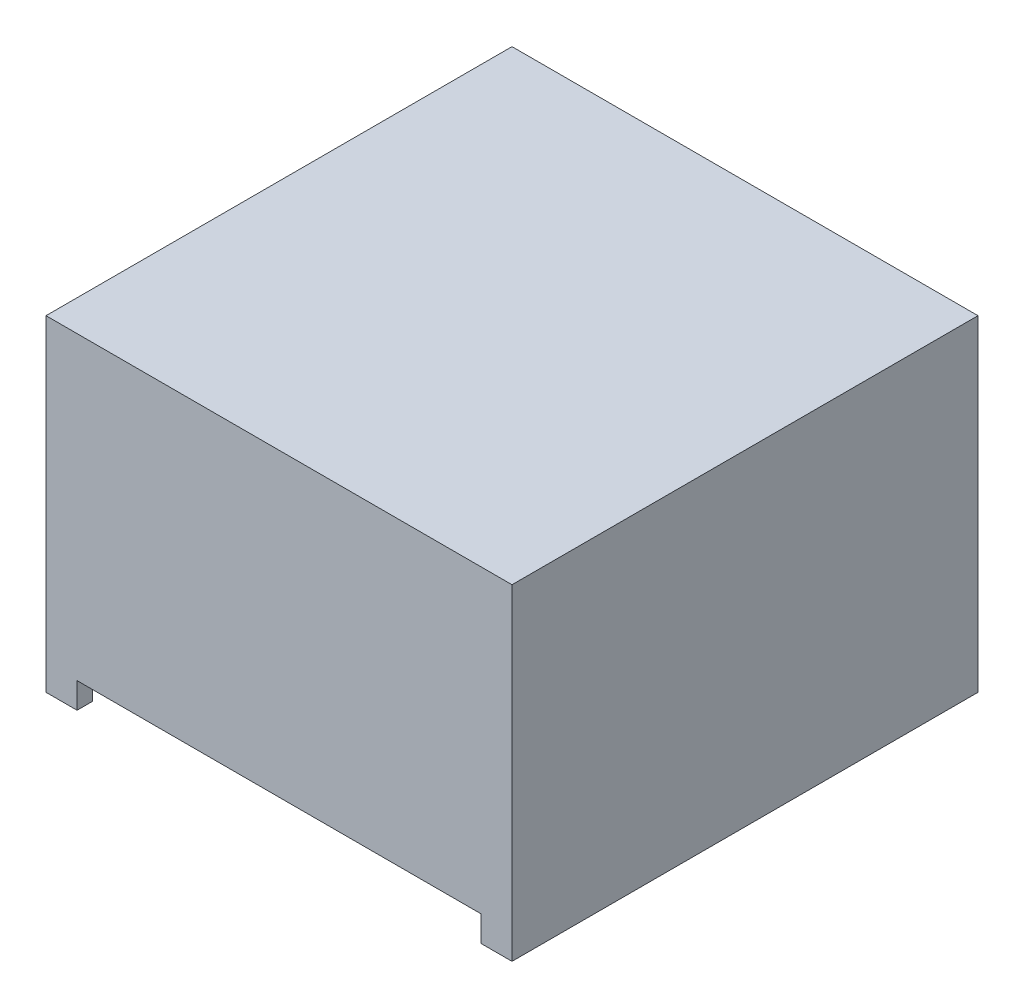
SolidWorks part; units mm, degrees
ref_plane "前视基准面" through (0, 0, 0) normal (0, 0, 1) x (1, 0, 0)
ref_plane "上视基准面" through (0, 0, 0) normal (0, 1, 0) x (1, 0, 0)
ref_plane "右视基准面" through (0, 0, 0) normal (1, 0, 0) x (0, 0, -1)
sketch "草图1" plane through (0, 0, 0) normal (0, 1, 0) x (1, 0, 0)
  line L1 (0, 0) -> (-150, 0)
  line L2 (0, 0) -> (0, -150)
  line L3 (0, -150) -> (-150, -150)
  line L4 (-150, 0) -> (-150, -150)
  line L5 (-5, -5) -> (-145, -5)
  line L6 (-5, -5) -> (-5, -145)
  line L7 (-5, -145) -> (-145, -145)
  line L8 (-145, -5) -> (-145, -145)
  point P9 (0, 0)
  dimension "D1" = 150
  dimension "D2" = 150
  dimension "D3" = 5
  dimension "D4" = 5
  dimension "D5" = 5
  dimension "D6" = 5
extrude "凸台-拉伸2" add sketch "草图1" along normal blind 5 contours L1 L4 L3 L2
extrude "凸台-拉伸3" add sketch "草图1<3>" against normal blind 100
sketch "草图1<3>" plane through (0, 0, 0) normal (0, 1, 0) x (1, 0, 0) same geometry as "草图1"
sketch "草图3" plane through (0, 0, 150) normal (0, 0, 1) x (1, 0, 0)
  line L0 (0, -100) -> (-150, -100) construction
  line L1 (-140, -100) -> (-10, -100)
  line L2 (-140, -100) -> (-140, -91.734)
  line L3 (-140, -91.734) -> (-10, -91.734)
  line L4 (-10, -100) -> (-10, -91.734)
  line L5 (-150, 5) -> (-150, -100) construction
  line L6 (0, 5) -> (0, -100) construction
  dimension "D1" = 10
  dimension "D2" = 10
extrude "切除-拉伸1" cut sketch "草图3" against normal blind 5
